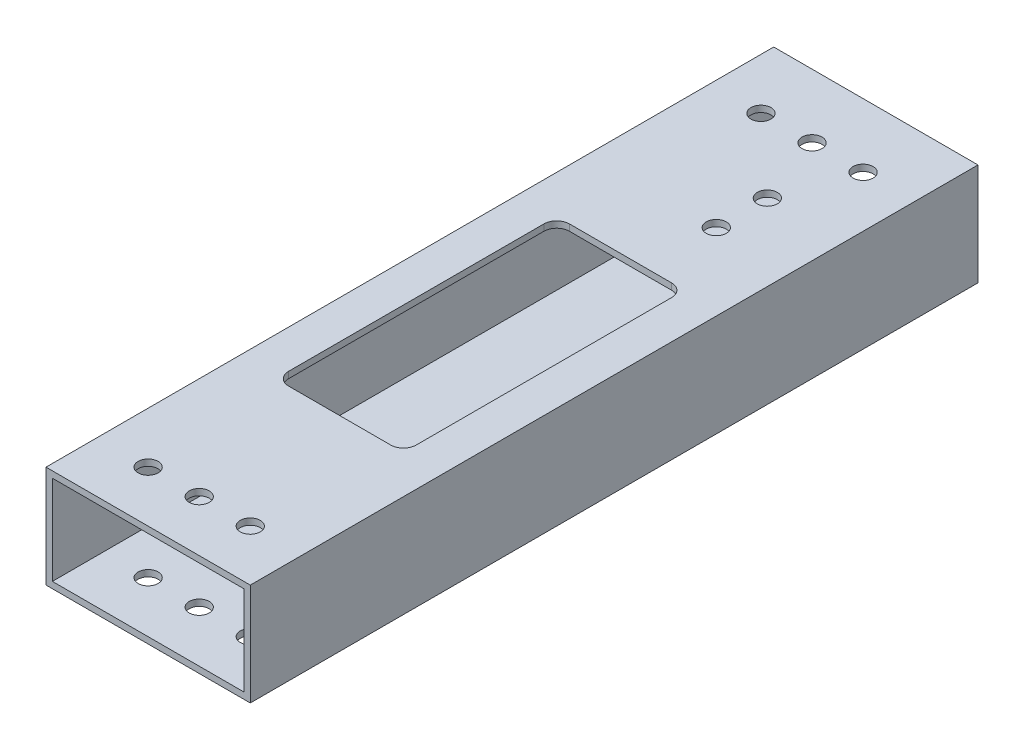
SolidWorks part; units mm, degrees
other "Markup4"
sketch "Sketch7" plane through (25.4, -12.7, 0) normal (0.9921, -0.1226, -0.0275) x (-0.1217, -0.992, 0.0335)
other "Markup5"
sketch "Sketch10"
material "6061-T6 (SS)"
ref_plane "Front Plane" through (0, 0, 0) normal (0, 0, 1) x (1, 0, 0)
ref_plane "Top Plane" through (0, 0, 0) normal (0, 1, 0) x (1, 0, 0)
ref_plane "Right Plane" through (0, 0, 0) normal (1, 0, 0) x (0, 0, -1)
sketch "Sketch1" plane through (0, 0, 0) normal (0, 0, 1) x (1, 0, 0)
  line L1 (-25.4, -12.7) -> (25.4, -12.7)
  line L2 (-25.4, -12.7) -> (-25.4, 12.7)
  line L3 (-25.4, 12.7) -> (25.4, 12.7)
  line L4 (25.4, -12.7) -> (25.4, 12.7)
  line L5 (-25.4, -12.7) -> (25.4, 12.7) construction
  line L6 (-25.4, 12.7) -> (25.4, -12.7) construction
  line L7 (-23.8125, -11.1125) -> (23.8125, -11.1125)
  line L8 (-23.8125, -11.1125) -> (-23.8125, 11.1125)
  line L9 (-23.8125, 11.1125) -> (23.8125, 11.1125)
  line L10 (23.8125, -11.1125) -> (23.8125, 11.1125)
  line L11 (-23.8125, -11.1125) -> (23.8125, 11.1125) construction
  line L12 (-23.8125, 11.1125) -> (23.8125, -11.1125) construction
  point P0 (0, 0)
  point P6 (0, 0)
  dimension "D1" = 50.8
  dimension "D2" = 25.4
  dimension "D3" = 1.5875
  dimension "D4" = 1.5875
extrude "Boss-Extrude1" add sketch "Sketch1" along normal blind 180.975
sketch "Sketch2" plane through (0, 12.7, 0) normal (0, 1, 0) x (1, 0, 0)
  line L0 (25.4, 0) -> (-25.4, 0) construction
  line L1 (-25.4, -180.975) -> (-25.4, 0) construction
  line L3 (25.4, -180.975) -> (-25.4, -180.975) construction
  circle A0 centre (-12.7, -15.875) radius 2.4892
  circle A1 centre (0, -15.875) radius 2.4892
  circle A2 centre (12.7, -15.875) radius 2.4892
  circle A3 centre (-12.7, -168.275) radius 2.4892
  circle A4 centre (0, -168.275) radius 2.4892
  circle A5 centre (12.7, -168.275) radius 2.4892
  circle A6 centre (6.35, -33.3375) radius 2.4892
  circle A7 centre (6.35, -46.0375) radius 2.4892
  point P23 (6.35, -46.0375)
  point P24 (0, 0)
  dimension "D1" = 4.9784
  dimension "D2" = 15.875
  dimension "D3" = 12.7
  dimension "D4" = 12.7
  dimension "D5" = 12.7
  dimension "D6" = 12.7
  dimension "D7" = 31.75
  dimension "D8" = 33.3375
extrude "Cut-Extrude1" cut sketch "Sketch2" against normal through all
sketch "Sketch9" plane through (0, 12.7, 0) normal (0, 1, 0) x (1, 0, 0)
  line L0 (25.4, 0) -> (-25.4, 0) construction
  line L1 (-15.875, -63.5) -> (15.875, -63.5)
  line L2 (-15.875, -63.5) -> (-15.875, -133.35)
  line L3 (-15.875, -133.35) -> (15.875, -133.35)
  line L4 (15.875, -63.5) -> (15.875, -133.35)
  line L5 (-25.4, -180.975) -> (-25.4, 0) construction
  dimension "D1" = 63.5
  dimension "D2" = 31.75
  dimension "D3" = 9.525
  dimension "D4" = 69.85
extrude "Cut-Extrude2" cut sketch "Sketch9" against normal up to surface (23.8125 mm away) up to face at (0, -11.1125, 18.3642)
fillet "Fillet1" radius 3.175 4 edges at (-15.875, 11.9062, 63.5) (15.875, 11.9062, 133.35) (-15.875, 11.9062, 133.35) (15.875, 11.9062, 63.5)
